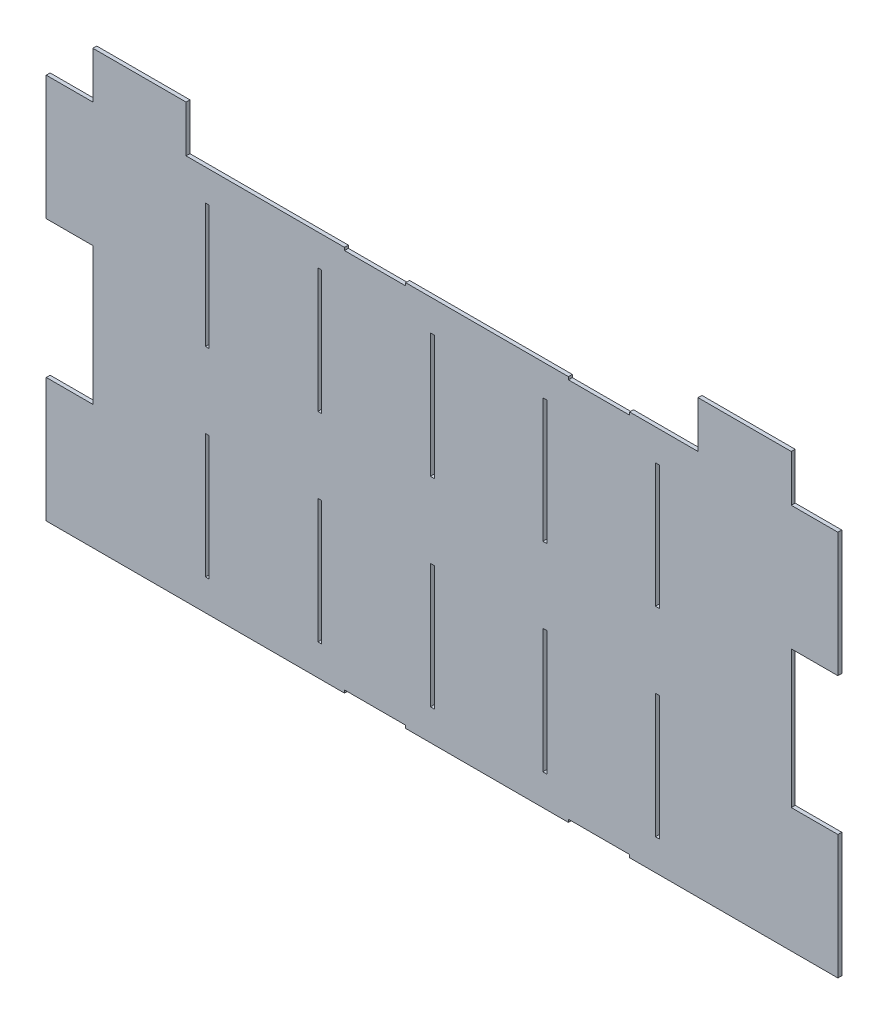
SolidWorks part; units mm, degrees
material "Custom Plastic"
ref_plane "X-Y Datum" through (0, 0, 0) normal (0, 0, 1) x (1, 0, 0)
ref_plane "X-Z Datum" through (0, 0, 0) normal (0, 1, 0) x (1, 0, 0)
ref_plane "Y-Z Datum" through (0, 0, 0) normal (1, 0, 0) x (0, 0, -1)
sketch "Sketch1" plane through (0, 0, 0) normal (0, 0, 1) x (1, 0, 0)
  line L0 (-285.4305, 0) -> (285.4305, 0) construction
  line L1 (-285.4305, -157.7875) -> (285.4305, -157.7875)
  line L2 (-285.4305, -157.7875) -> (-285.4305, 157.7875)
  line L3 (-285.4305, 157.7875) -> (285.4305, 157.7875)
  line L4 (285.4305, -157.7875) -> (285.4305, 157.7875)
  line L5 (-285.4305, -157.7875) -> (285.4305, 157.7875) construction
  line L6 (-285.4305, 157.7875) -> (285.4305, -157.7875) construction
  line L7 (-282.2555, -154.615) -> (-282.2555, 154.615)
  line L8 (-280.6655, -153.025) -> (-195.0655, -153.025)
  line L9 (-280.6655, -153.025) -> (-280.6655, 153.025)
  line L10 (-280.6655, 153.025) -> (-195.0655, 153.025)
  line L11 (-195.0655, -153.025) -> (-195.0655, 153.025)
  line L12 (-280.6655, -153.025) -> (-195.0655, 153.025) construction
  line L13 (-280.6655, 153.025) -> (-195.0655, -153.025) construction
  line L14 (-282.2555, 154.615) -> (-193.4755, 154.615)
  line L15 (-193.4755, -154.615) -> (-193.4755, 154.615)
  line L16 (-282.2555, -154.615) -> (-193.4755, -154.615)
  line L17 (-190.3005, 154.615) -> (-101.5205, 154.615)
  line L18 (-188.7105, 153.025) -> (-103.1105, 153.025)
  line L19 (-190.3005, -154.615) -> (-190.3005, 154.615)
  line L20 (-188.7105, -153.025) -> (-188.7105, 153.025)
  line L21 (-101.5205, -154.615) -> (-101.5205, 154.615)
  line L22 (-103.1105, -153.025) -> (-103.1105, 153.025)
  line L23 (-188.7105, -153.025) -> (-103.1105, -153.025)
  line L24 (-190.3005, -154.615) -> (-101.5205, -154.615)
  line L25 (-188.7105, -153.025) -> (-103.1105, 153.025) construction
  line L26 (-188.7105, 153.025) -> (-103.1105, -153.025) construction
  line L27 (-98.3455, 154.615) -> (-9.5655, 154.615)
  line L28 (-96.7555, 153.025) -> (-11.1555, 153.025)
  line L29 (-98.3455, -154.615) -> (-98.3455, 154.615)
  line L30 (-96.7555, -153.025) -> (-96.7555, 153.025)
  line L31 (-9.5655, -154.615) -> (-9.5655, 154.615)
  line L32 (-11.1555, -153.025) -> (-11.1555, 153.025)
  line L33 (-96.7555, -153.025) -> (-11.1555, -153.025)
  line L34 (-98.3455, -154.615) -> (-9.5655, -154.615)
  line L35 (-96.7555, -153.025) -> (-11.1555, 153.025) construction
  line L36 (-96.7555, 153.025) -> (-11.1555, -153.025) construction
  line L37 (-6.3905, 154.615) -> (82.3895, 154.615)
  line L38 (-4.8005, 153.025) -> (80.7995, 153.025)
  line L39 (-6.3905, -154.615) -> (-6.3905, 154.615)
  line L40 (-4.8005, -153.025) -> (-4.8005, 153.025)
  line L41 (82.3895, -154.615) -> (82.3895, 154.615)
  line L42 (80.7995, -153.025) -> (80.7995, 153.025)
  line L43 (-4.8005, -153.025) -> (80.7995, -153.025)
  line L44 (-6.3905, -154.615) -> (82.3895, -154.615)
  line L45 (-4.8005, -153.025) -> (80.7995, 153.025) construction
  line L46 (-4.8005, 153.025) -> (80.7995, -153.025) construction
  line L47 (85.5645, 154.615) -> (174.3445, 154.615)
  line L48 (87.1545, 153.025) -> (172.7545, 153.025)
  line L49 (85.5645, -154.615) -> (85.5645, 154.615)
  line L50 (87.1545, -153.025) -> (87.1545, 153.025)
  line L51 (174.3445, -154.615) -> (174.3445, 154.615)
  line L52 (172.7545, -153.025) -> (172.7545, 153.025)
  line L53 (87.1545, -153.025) -> (172.7545, -153.025)
  line L54 (85.5645, -154.615) -> (174.3445, -154.615)
  line L55 (87.1545, -153.025) -> (172.7545, 153.025) construction
  line L56 (87.1545, 153.025) -> (172.7545, -153.025) construction
  point P0 (0, 0)
  point P8 (-237.8655, 0)
  dimension "D1" = 570.861
  dimension "D2" = 315.575
  dimension "D3" = 306.05
  dimension "D4" = 85.6
  dimension "D5" = 3.175
  dimension "D8" = 3.175
  dimension "D6" = 1.59
  dimension "D7" = 5
extrude "Boss-Extrude1" add sketch "Sketch1" along normal blind 3.175 contours L8 L11 L10 L9 | L20 L23 L22 L18 | L30 L33 L32 L28 | L50 L53 L52 L48 | L49 L54 L51 L47 L53 L50 L48 L52 | L1 L4 L3 L2 L54 L49 L47 L51 L44 L39 L37 L41 L34 L29 L27 L31 L24 L19 L17 L21 L16 L7 L14 L15 | L40 L43 L42 L38 | L7 L16 L15 L14 L11 L8 L9 L10 | L19 L24 L21 L17 L23 L20 L18 L22 | L29 L34 L31 L27 L33 L30 L28 L32 | L39 L44 L41 L37 L43 L40 L38 L42 region at (-284.7782, 0, 0) region at (-281.9338, 0, 0) region at (-237.8655, 0, 0) region at (-145.9105, 154.2933, 0) region at (-145.9105, 0, 0) region at (-53.9555, 154.2933, 0) region at (-53.9555, 0, 0) region at (37.9995, 154.2933, 0) region at (37.9995, 0, 0) region at (129.9545, 154.2933, 0) region at (129.9545, 0, 0)
sketch "Sketch2" plane through (0, 0, 3.175) normal (0, 0, 1) x (1, 0, 0)
  line L0 (-190.3005, -154.615) -> (-193.4755, -154.615) construction
  line L1 (-191.888, -154.615) -> (-191.888, 157.7875) construction
  line L2 (-285.4305, 157.7875) -> (285.4305, 157.7875) construction
  line L4 (-193.4755, -30.7875) -> (-190.3005, -30.7875)
  line L5 (-193.4755, -30.7875) -> (-193.4755, -132.3875)
  line L6 (-193.4755, -132.3875) -> (-190.3005, -132.3875)
  line L7 (-190.3005, -30.7875) -> (-190.3005, -132.3875)
  line L8 (-193.4755, -30.7875) -> (-190.3005, -132.3875) construction
  line L9 (-193.4755, -132.3875) -> (-190.3005, -30.7875) construction
  line L12 (-285.4305, -157.7875) -> (285.4305, -157.7875) construction
  point P8 (-191.888, -81.5875)
  dimension "D1" = 76.2
  dimension "D2" = 3.175
  dimension "D3" = 101.6
extrude "Cut-Extrude1" cut sketch "Sketch2" against normal blind 3.175
sketch "Sketch7" plane through (0, 0, 3.175) normal (0, 0, 1) x (1, 0, 0)
  line L1 (103.2695, -155.5015) -> (153.2695, -155.5015)
  line L2 (103.2695, -155.5015) -> (103.2695, -157.7875)
  line L3 (103.2695, -157.7875) -> (153.2695, -157.7875)
  line L4 (153.2695, -155.5015) -> (153.2695, -157.7875)
  line L5 (-79.7305, -155.5015) -> (-29.7305, -155.5015)
  line L6 (-79.7305, -155.5015) -> (-79.7305, -157.7875)
  line L7 (-79.7305, -157.7875) -> (-29.7305, -157.7875)
  line L8 (-29.7305, -155.5015) -> (-29.7305, -157.7875)
extrude "Cut-Extrude5" cut sketch "Sketch7" against normal blind 3.175
mirror "Mirror3" about plane through (0, 0, 0) normal (0, 1, 0) of "Cut-Extrude1"
pattern_linear "LPattern2" count 5 spacing 91.96 along (1, 0, 0) of "Mirror3"
sketch "Sketch9" plane through (0, 0, 0) normal (0, 0, -1) x (-1, 0, 0)
  line L0 (-304.4805, -56.1875) -> (-304.4805, -157.7875) construction
  line L9 (-285.4305, 157.7875) -> (-209.2305, 157.7875)
  line L10 (-285.4305, 157.7875) -> (-285.4305, 195.8875)
  line L11 (-285.4305, 195.8875) -> (-209.2305, 195.8875)
  line L12 (-209.2305, 157.7875) -> (-209.2305, 195.8875)
  line L13 (-285.4305, 157.7875) -> (-323.5305, 157.7875)
  line L14 (-285.4305, 157.7875) -> (-285.4305, 56.1875)
  line L15 (-285.4305, 56.1875) -> (-323.5305, 56.1875)
  line L16 (-323.5305, 157.7875) -> (-323.5305, 56.1875)
  line L17 (-323.5305, 106.9875) -> (-285.4305, 106.9875) construction
  line L18 (-304.4805, 157.7875) -> (-304.4805, 113.3375)
  line L19 (-304.4805, 113.3375) -> (-304.4805, 56.1875) construction
  line L20 (-285.4305, -157.7875) -> (-323.5305, -157.7875)
  line L21 (-285.4305, -157.7875) -> (-285.4305, -88.7618)
  line L25 (-285.4305, -88.7618) -> (-285.4305, -56.1875)
  line L26 (-285.4305, -56.1875) -> (-323.5305, -56.1875)
  line L28 (-323.5305, -56.1875) -> (-323.5305, -157.7875)
  line L29 (-323.5305, -106.9875) -> (-285.4305, -106.9875) construction
  line L30 (-304.4805, -56.1875) -> (-304.4805, -106.9875) construction
  line L31 (-304.4805, -106.9875) -> (-304.4805, -157.7875) construction
  line L32 (-304.4805, -56.1875) -> (-304.4805, -106.9875) construction
  line L33 (-304.4805, -106.9875) -> (-304.4805, -157.7875) construction
  circle A0 centre (-304.4805, 135.5625) radius 3 construction
  circle A1 centre (-304.4805, 84.7625) radius 3 construction
  circle A2 centre (-304.4805, -81.5875) radius 3 construction
  circle A3 centre (-304.4805, -132.3875) radius 3 construction
  dimension "D1" = 6
  dimension "D2" = 6
  dimension "D3" = 76.2
  dimension "D4" = 38.1
  dimension "D5" = 101.6
  dimension "D6" = 38.1
  dimension "D7" = 38.1
  dimension "D8" = 101.6
extrude "Boss-Extrude3" add sketch "Sketch9" against normal blind 3.175 contours L13 L16 L15 L14 | L9 L12 L11 L10 | L26 L28 L20 L21 L25 A3 A2 region at (247.3305, 176.8375, 0) region at (304.4805, 106.9875, 0) region at (304.4805, -106.9875, 0)
mirror "Mirror4" about plane through (0, 0, 0) normal (1, 0, 0) of "Boss-Extrude3"
mirror "Mirror5" about plane through (0, 0, 0) normal (0, 1, 0) of "Cut-Extrude5"
